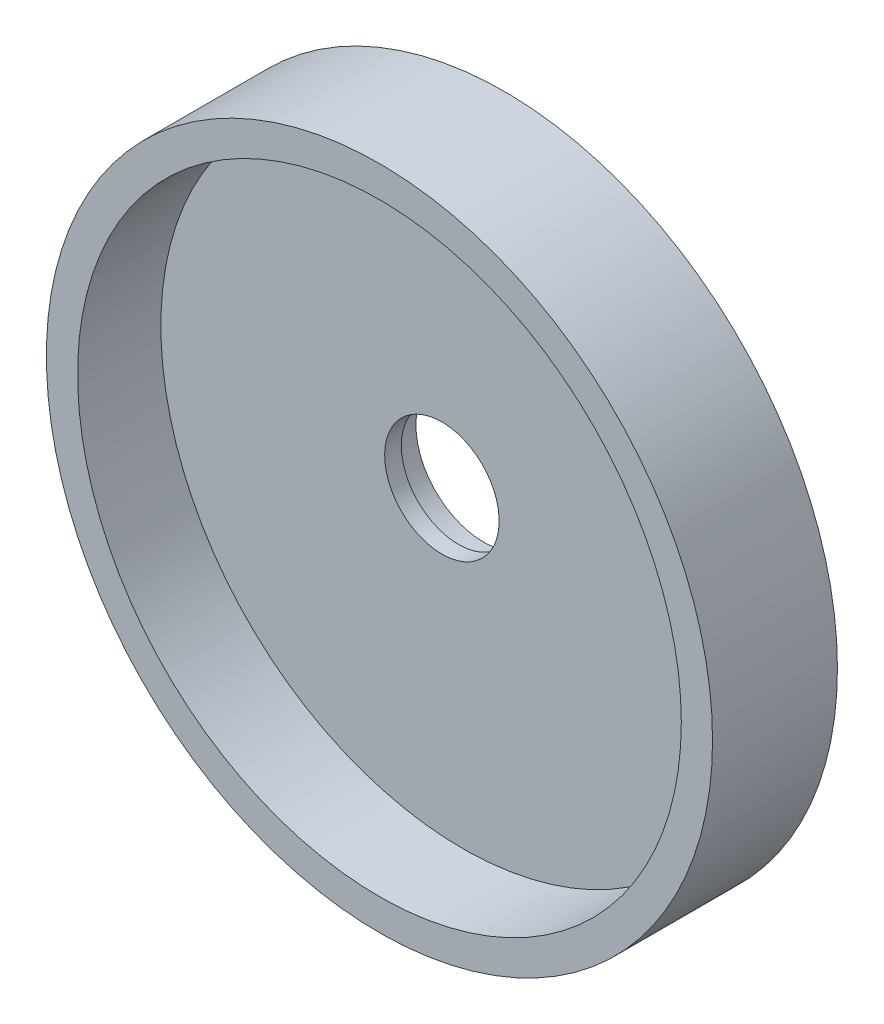
SolidWorks part; units mm, degrees
ref_plane "Front Plane" through (0, 0, 0) normal (0, 0, 1) x (1, 0, 0)
ref_plane "Top Plane" through (0, 0, 0) normal (0, 1, 0) x (1, 0, 0)
ref_plane "Right Plane" through (0, 0, 0) normal (1, 0, 0) x (0, 0, -1)
sketch "Sketch1" plane through (0, 0, 0) normal (0, 0, 1) x (1, 0, 0)
  line L0 (0, 16) -> (0, -16) construction
  circle A0 centre (0, 0) radius 16
  dimension "D1" = 32
extrude "Boss-Extrude1" add sketch "Sketch1" along normal blind 6
sketch "Sketch3" plane through (0, 0, 6) normal (0, 0, 1) x (1, 0, 0)
  circle A0 centre (0, 0) radius 14.5
  dimension "D1" = 29
extrude "Cut-Extrude1" cut sketch "Sketch3" against normal blind 4
sketch "Sketch4" plane through (0, 0, 0) normal (0, 0, -1) x (-1, 0, 0)
  line L0 (16, 0) -> (1, 0) construction
  circle A3 centre (0, 0) radius 16 construction
  circle A4 centre (1, 0) radius 2.75
  dimension "D1" = 15
  dimension "D2" = 5.5
extrude "Cut-Extrude2" cut sketch "Sketch4" against normal blind 2
sketch "Sketch6" plane through (0, 0, 0) normal (0, 0, -1) x (-1, 0, 0)
  line L0 (-2.25, 0) -> (-1.75, 0) construction
  circle A0 centre (1, 0) radius 3.25
  circle A1 centre (1, 0) radius 2.75 construction
  dimension "D1" = 0.5
extrude "Cut-Extrude3" cut sketch "Sketch6" against normal blind 1.2
ref_axis "Axis1" through (-1, 0, 1.2) along (0, 0, -1)
draft "Draft4" type of draft neutral plane draft angle 3 faces to draft 1 face at (-4.25, 0, 1.2) neutral plane through (0, 0, 0) neutral plane normal (0, 0, -1) parameters "D1"=3
